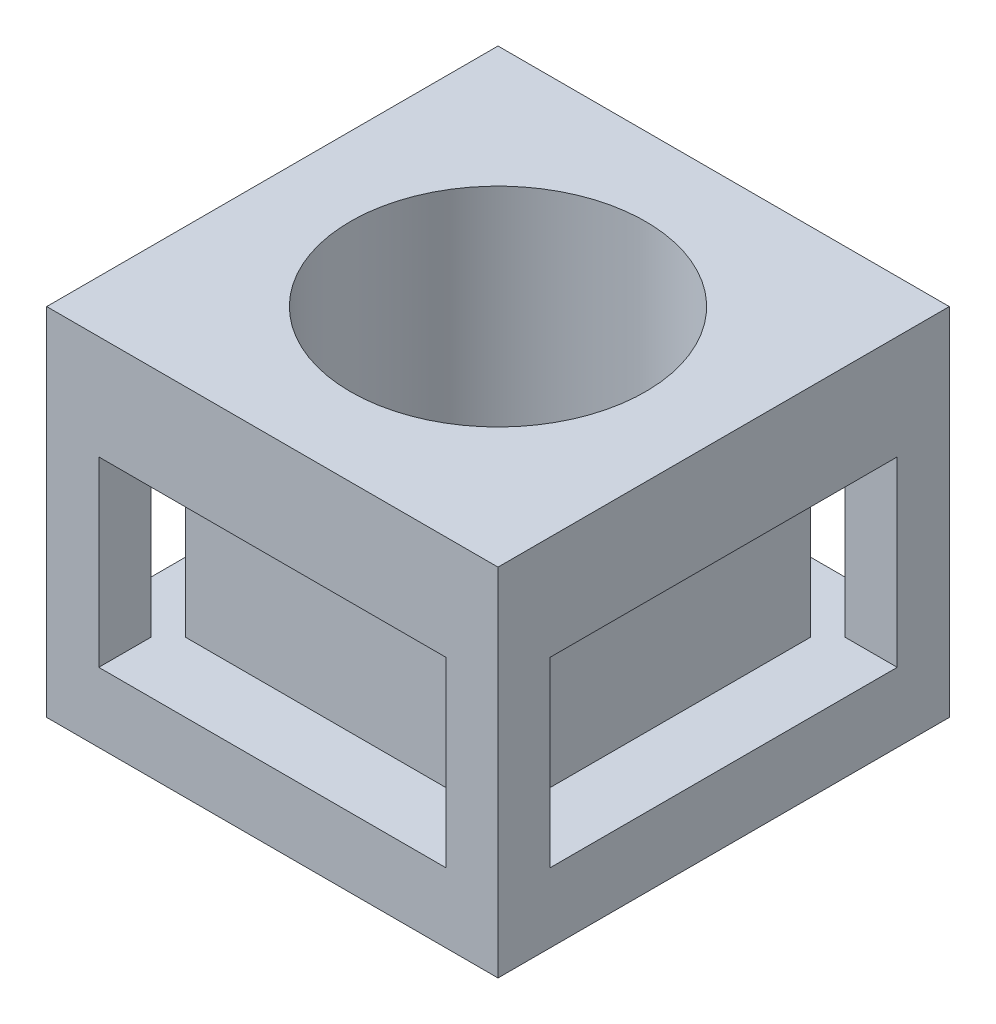
SolidWorks part; units mm, degrees
ref_plane "Front Plane" through (0, 0, 0) normal (0, 0, 1) x (1, 0, 0)
ref_plane "Top Plane" through (0, 0, 0) normal (0, 1, 0) x (1, 0, 0)
ref_plane "Right Plane" through (0, 0, 0) normal (1, 0, 0) x (0, 0, -1)
sketch "Sketch2" plane through (0, 0, 0) normal (0, 0, 1) x (1, 0, 0)
  line L1 (0, 0) -> (26, 0)
  line L2 (0, 0) -> (0, 20.5)
  line L3 (0, 20.5) -> (26, 20.5)
  line L4 (26, 0) -> (26, 20.5)
  dimension "W" = 26
  dimension "H" = 20.5
extrude "Boss-Extrude1" add sketch "Sketch2" along normal blind 26
ref_point "Point2"
sketch "Haptuator Hole" plane through (0, 20.5, 0) normal (0, 1, 0) x (1, 0, 0)
  circle A0 centre (13, -13) radius 8.5
  dimension "D" = 17
extrude "HaptuatorInsertion" cut sketch "Haptuator Hole" against normal blind 12.5
ref_point "Point3"
sketch "Sketch8" plane through (0, 0, 0) normal (0, -1, 0) x (1, 0, 0)
  circle A0 centre (13, 13) radius 3.9898
extrude "Clearance" cut sketch "Sketch8" against normal through all contours A0
ref_plane "Plane5" through (13, 0, 0) normal (1, 0, 0) x (0, 0, -1)
ref_plane "Plane6" through (0, 0, 13) normal (0, 0, 1) x (1, 0, 0)
ref_axis "Axis2" through (13, -1.025, 13) along (0, 1, 0)
sketch "cutout" plane through (0, 0, 26) normal (0, 0, 1) x (1, 0, 0)
  line L0 (26, 20.5) -> (0, 20.5) construction
  line L1 (23, 14.5) -> (3, 14.5)
  line L2 (23, 14.5) -> (23, 4)
  line L3 (23, 4) -> (3, 4)
  line L4 (3, 14.5) -> (3, 4)
  line L7 (13, -11.275) -> (13, 11.275) construction
  dimension "cutW" = 20
  dimension "cutH" = 10.5
  dimension "cutHOffset" = 6
  dimension "cutWOffset" = 10
extrude "Cut-Extrude3" cut sketch "cutout" against normal blind 4
pattern_circular "CirPattern1" count 4 over 360 about axis through (13, -1.025, 13) along (0, 1, 0) of "Cut-Extrude3"
equation "\"L\"= 29'Haptuator Length"
equation "\"W\" = 26'ClampWidth"
equation "\"H\"= \"L\" / 2 + 6'ClampHeight"
equation "\"D\"= 17'Haptuator Clearance Diam"
equation "\"depth\"= \"L\" / 2 - 2mm'Insertion Depth"
equation "\"clearD\"= 6mm'Clearance hole Diam for Actuator"
equation "\"cutD\" = 4mm'depth for weight cut and zip tie access"
equation "\"cutW\" = \"W\" - 6mm"
equation "\"cutH\" = \"H\" - 10mm"
equation "\"cutWOffset\"= \"cutW\" / 2'cut offset from center of housing"
equation "\"cutHOffset\"= 6mm'distance from cut to edge"
